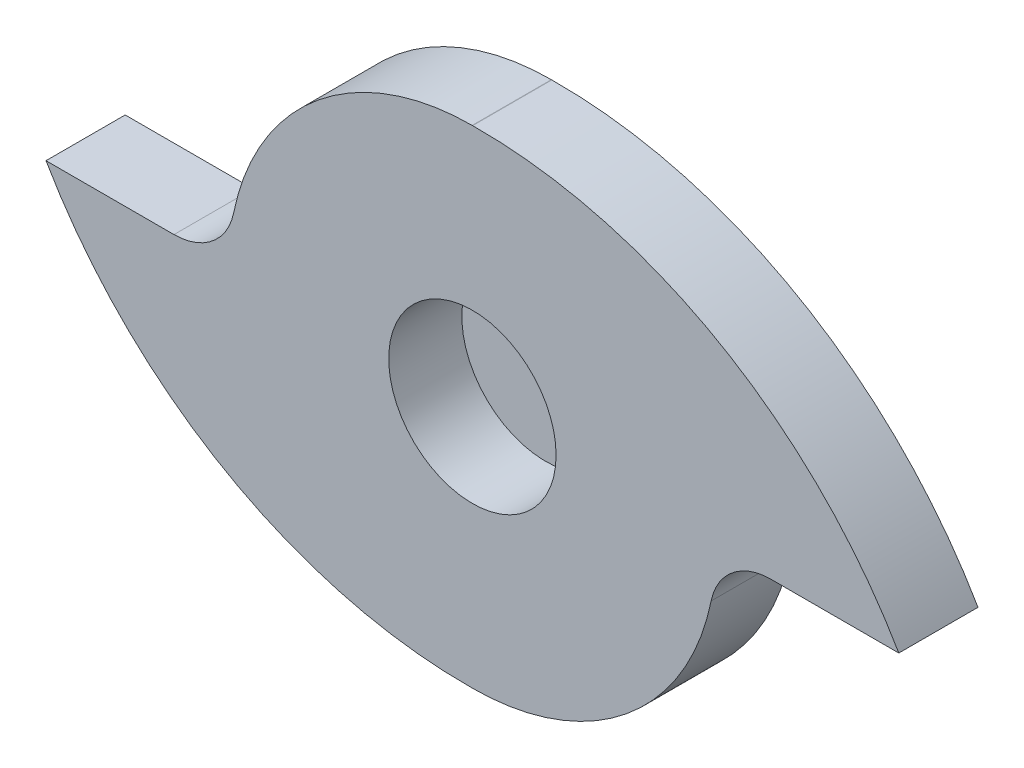
SolidWorks part; units mm, degrees
ref_plane "Front Plane" through (0, 0, 0) normal (0, 0, 1) x (1, 0, 0)
ref_plane "Top Plane" through (0, 0, 0) normal (0, 1, 0) x (1, 0, 0)
ref_plane "Right Plane" through (0, 0, 0) normal (1, 0, 0) x (0, 0, -1)
sketch "Sketch1" plane through (0, 0, 0) normal (0, 0, 1) x (1, 0, 0)
  line L0 (-40, 0) -> (-70, 0)
  line L1 (40, 0) -> (70, 0)
  line L2 (0, -14.8983) -> (0, 14.8983) construction
  line L3 (-20.6072, 0) -> (20.6072, 0) construction
  arc A0 (0, 40) -> (-40, 0) centre (0, 0) ccw
  arc A2 (-70, 0) -> (0, -40) centre (-0.6937, 40.036) ccw
  arc A3 (0, -40) -> (40, 0) centre (0, 0) ccw
  circle A4 centre (0, 0) radius 2.5
  arc A6 (70, 0) -> (0, 40) centre (0.6937, -40.036) ccw
  point P13 (0, 0)
  point P15 (0, 0)
  dimension "D1" = 30
  dimension "D3" = 80
extrude "Boss-Extrude1" add sketch "Sketch1" along normal blind 13 contours A2 A3 L1 A6 A0 L0
sketch "Sketch3" plane through (0, 0, 13) normal (0, 0, 1) x (1, 0, 0)
  circle A0 centre (0, 0) radius 13.74
extrude "Cut-Extrude2" cut sketch "Sketch3" against normal blind 12 contours A0
sketch "Sketch6" plane through (0, 0, 0) normal (0, 0, -1) x (-1, 0, 0)
  circle A0 centre (0, 0) radius 2.55
  dimension "D1" = 5.1
extrude "Cut-Extrude3" cut sketch "Sketch6" against normal up to surface (1 mm away) up to face at (13.74, 0, 1)
fillet "Fillet1" radius 10 4 edges at (0, -40, 6.5) (40, 0, 6.5) (0, 40, 6.5) (-40, 0, 6.5)
